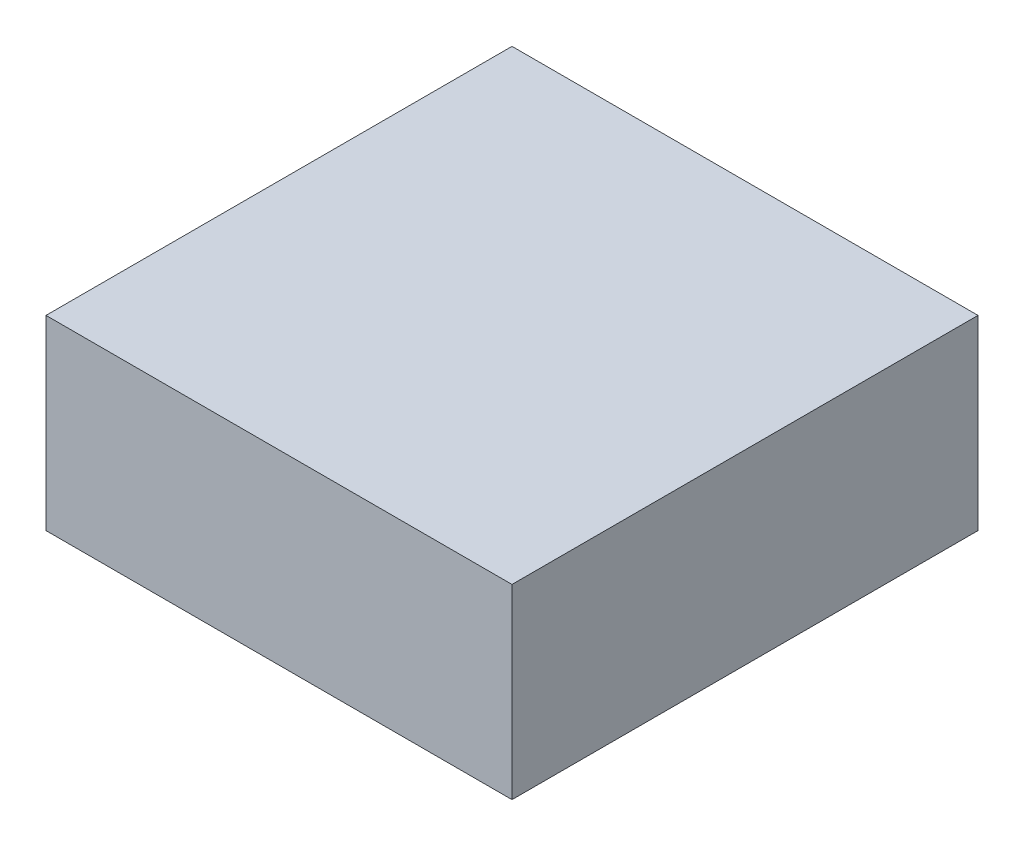
SolidWorks part; units mm, degrees
ref_plane "Front Plane" through (0, 0, 0) normal (0, 0, 1) x (1, 0, 0)
ref_plane "Top Plane" through (0, 0, 0) normal (0, 1, 0) x (1, 0, 0)
ref_plane "Right Plane" through (0, 0, 0) normal (1, 0, 0) x (0, 0, -1)
sketch "Sketch1" plane through (0, 0, 0) normal (0, 1, 0) x (1, 0, 0)
  line L1 (-65, 65) -> (65, 65)
  line L2 (-65, 65) -> (-65, -65)
  line L3 (-65, -65) -> (65, -65)
  line L4 (65, 65) -> (65, -65)
  line L5 (-65, 65) -> (65, -65) construction
  line L6 (-65, -65) -> (65, 65) construction
  point P0 (0, 0)
  dimension "D1" = 130
  dimension "D2" = 130
extrude "Boss-Extrude1" add sketch "Sketch1" along normal blind 52
